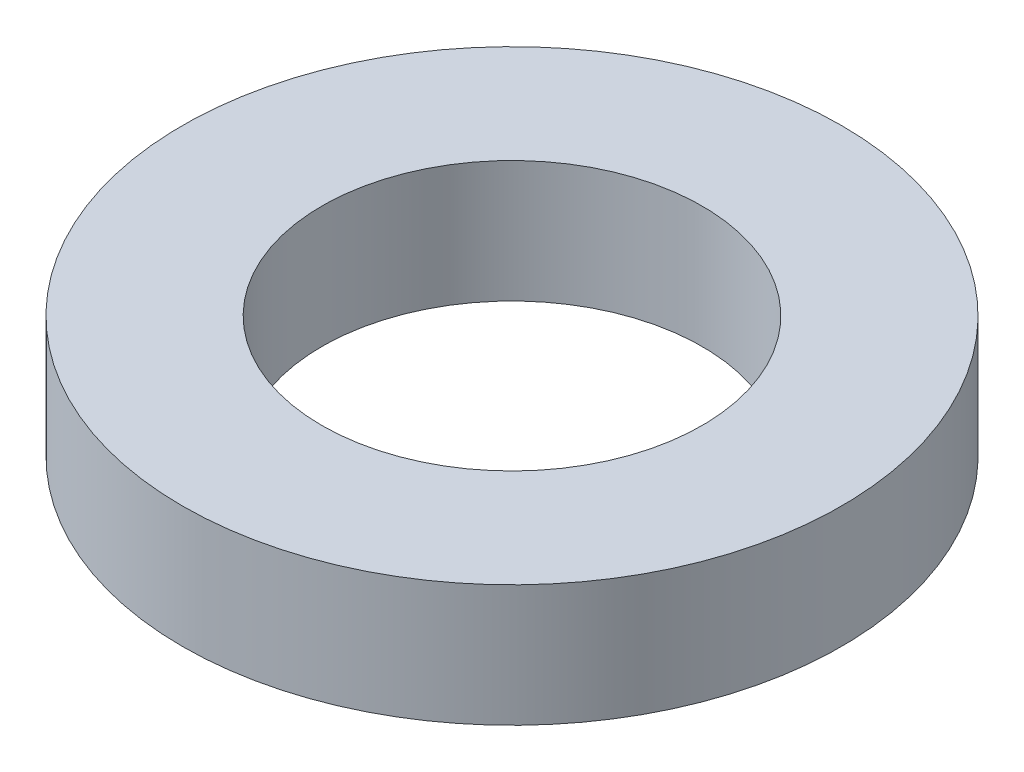
SolidWorks part; units mm, degrees
ref_plane "Front Plane" through (0, 0, 0) normal (0, 0, 1) x (1, 0, 0)
ref_plane "Top Plane" through (0, 0, 0) normal (0, 1, 0) x (1, 0, 0)
ref_plane "Right Plane" through (0, 0, 0) normal (1, 0, 0) x (0, 0, -1)
sketch "Sketch1" plane through (0, 0, 0) normal (0, 1, 0) x (1, 0, 0)
  circle A0 centre (0, 0) radius 65
  dimension "FLANGE_OD" = 130
extrude "Boss-Extrude1" add sketch "Sketch1" along normal blind 24
sketch "Sketch2" plane through (0, 0, 0) normal (0, 1, 0) x (1, 0, 0)
  circle A0 centre (0, 0) radius 37.5
  dimension "BORE_D" = 75
extrude "Cut-Extrude1" cut sketch "Sketch2" along normal through all
sketch "Sketch3" plane through (0, 24, 0) normal (0, 1, 0) x (1, 0, 0)
  circle A0 centre (0, 0) radius 23.6696 construction
  circle A1 centre (-23.6696, 0) radius 4.7452
  dimension "BOLT_D" = 9.4904
  dimension "BOLT_PCD" = 47.3392
extrude "Cut-Extrude2" cut sketch "Sketch3" against normal blind 23.6939 rebuild error yes
pattern_circular "CirPattern1" count 5 over 360 rebuild error yes
